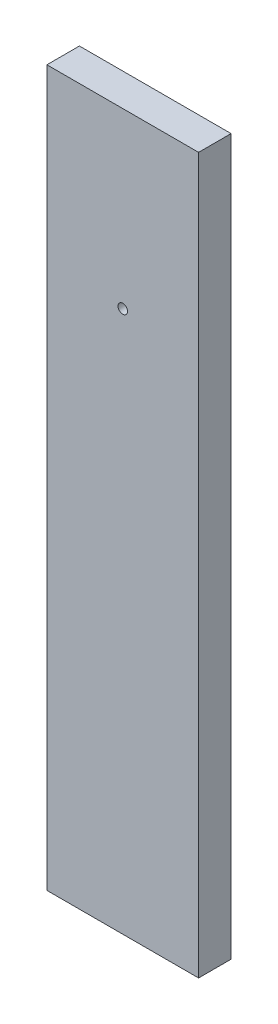
SolidWorks part; units mm, degrees
ref_plane "Front Plane" through (0, 0, 0) normal (0, 0, 1) x (1, 0, 0)
ref_plane "Top Plane" through (0, 0, 0) normal (0, 1, 0) x (1, 0, 0)
ref_plane "Right Plane" through (0, 0, 0) normal (1, 0, 0) x (0, 0, -1)
sketch "Sketch1" plane through (0, 0, 0) normal (0, 1, 0) x (1, 0, 0)
  line L1 (0, 0) -> (88.9, 0)
  line L2 (0, 0) -> (0, 19.05)
  line L3 (0, 19.05) -> (88.9, 19.05)
  line L4 (88.9, 0) -> (88.9, 19.05)
  dimension "D1" = 19.05
  dimension "D2" = 88.9
extrude "Boss-Extrude1" add sketch "Sketch1" along normal blind 419.1
sketch "Sketch2" plane through (0, 0, 0) normal (0, 0, 1) x (1, 0, 0)
  line L0 (44.45, 419.1) -> (44.45, 248.2649) construction
  line L1 (0, 419.1) -> (88.9, 419.1) construction
  circle A0 centre (44.45, 317.5) radius 2.7781
  point P6 (0, 0)
  dimension "D1" = 5.5562
  dimension "D2" = 101.6
extrude "Cut-Extrude1" cut sketch "Sketch2" against normal through all
